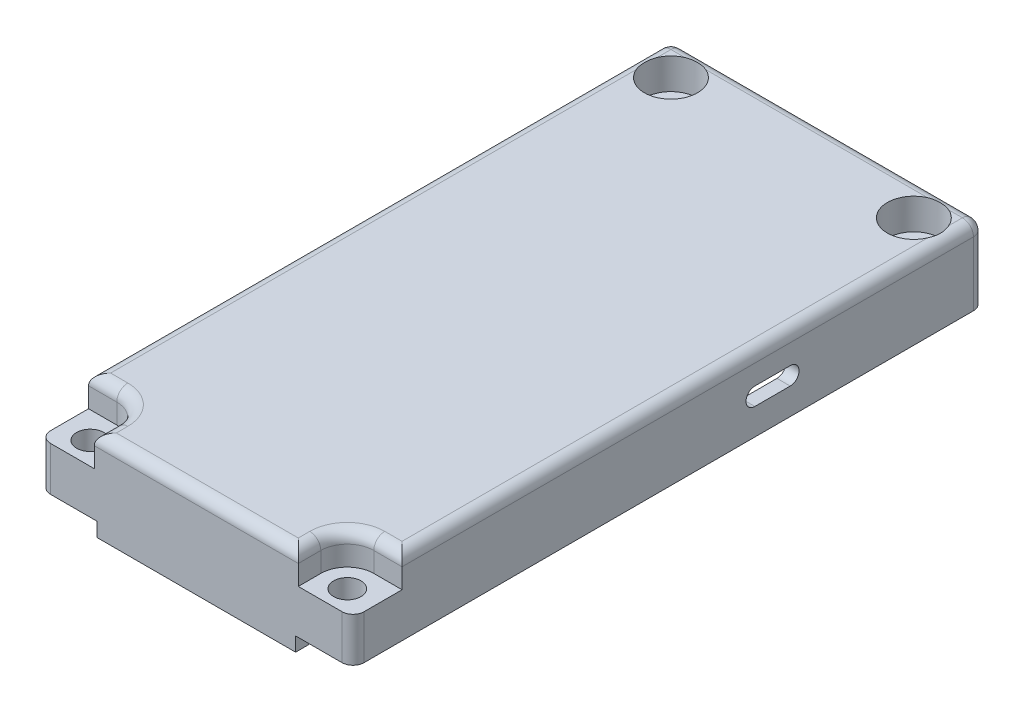
SolidWorks part; units mm, degrees
ref_plane "Front Plane" through (0, 0, 0) normal (0, 0, 1) x (1, 0, 0)
ref_plane "Top Plane" through (0, 0, 0) normal (0, 1, 0) x (1, 0, 0)
ref_plane "Right Plane" through (0, 0, 0) normal (1, 0, 0) x (0, 0, -1)
sketch "Sketch1" plane through (0, 0, 0) normal (0, 1, 0) x (1, 0, 0)
  line L1 (0, 0) -> (35.5, 0)
  line L2 (0, 0) -> (0, 71.5)
  line L3 (0, 71.5) -> (35.5, 71.5)
  line L4 (35.5, 0) -> (35.5, 71.5)
  dimension "D1" = 71.5
  dimension "D2" = 35.5
extrude "Boss-Extrude1" add sketch "Sketch1" along normal blind 8.5
sketch "Sketch2" plane through (0, 0, 0) normal (0, -1, 0) x (1, 0, 0)
  line L0 (0, -71.5) -> (0, 0) construction
  line L1 (1.5, -1.5) -> (34, -1.5)
  line L2 (1.5, -1.5) -> (1.5, -64.25)
  line L3 (1.5, -64.25) -> (34, -64.25)
  line L4 (34, -1.5) -> (34, -64.25)
  line L5 (0, 0) -> (35.5, 0) construction
  line L6 (35.5, 0) -> (35.5, -71.5) construction
  line L7 (35.5, -71.5) -> (0, -71.5) construction
  dimension "D1" = 1.5
  dimension "D2" = 1.5
  dimension "D3" = 1.5
  dimension "D4" = 7.25
extrude "Cut-Extrude1" cut sketch "Sketch2" against normal offset from surface (7 mm away) 1.5 up to face at (17.75, 8.5, -35.75)
sketch "Sketch3" plane through (0, 0, 0) normal (0, -1, 0) x (-1, 0, 0)
  line L0 (0, 0) -> (-35.5, 0) construction
  line L1 (-6.5, 0) -> (-29, 0)
  line L2 (-6.5, 0) -> (-6.5, 1.5)
  line L3 (-6.5, 1.5) -> (-29, 1.5)
  line L4 (-29, 0) -> (-29, 1.5)
  line L5 (-1.5, 1.5) -> (-34, 1.5) construction
  line L15 (-34, 64.25) -> (-34, 1.5) construction
  line L16 (-1.5, 1.5) -> (-1.5, 64.25) construction
  dimension "D1" = 5
  dimension "D2" = 5
extrude "Boss-Extrude2" add sketch "Sketch3" along normal blind 1.6
sketch "Sketch4" plane through (0, 0, -71.5) normal (0, 0, -1) x (-1, 0, 0)
  line L0 (-35.5, 0) -> (0, 0) construction
  line L1 (-25.5, 0) -> (-10, 0)
  line L2 (-25.5, 0) -> (-25.5, 1.25)
  line L3 (-25.5, 1.25) -> (-10, 1.25)
  line L4 (-10, 0) -> (-10, 1.25)
  line L7 (-35.5, 8.5) -> (-35.5, 0) construction
  line L8 (0, 8.5) -> (0, 0) construction
  dimension "D1" = 10
  dimension "D2" = 10
  dimension "D3" = 1.25
extrude "Cut-Extrude2" cut sketch "Sketch4" against normal blind 6.5
fillet "Fillet1" radius 1.25 2 edges at (25.5, 1.25, -68.25) (10, 1.25, -68.25)
sketch "Sketch5" plane through (0, 0, 0) normal (0, -1, 0) x (1, 0, 0)
  line L1 (13.25, -65) -> (22.25, -65)
  line L2 (13.25, -65) -> (13.25, -64.25)
  line L3 (13.25, -64.25) -> (22.25, -64.25)
  line L4 (22.25, -65) -> (22.25, -64.25)
  line L6 (34, -64.25) -> (1.5, -64.25) construction
  line L7 (25.5, -65) -> (10, -65) construction
  line L8 (34, -1.5) -> (34, -64.25) construction
  point P5 (0, 0)
  point P7 (0, 0)
  point P12 (17.75, -64.25)
  dimension "D1" = 9
  dimension "D2" = 16.25
extrude "Boss-Extrude3" add sketch "Sketch5" along normal blind 1.6
sketch "Sketch7" plane through (0, 7, 0) normal (0, -1, 0) x (1, 0, 0)
  line L0 (34, -1.5) -> (29, -1.5) construction
  line L1 (28, -1.5) -> (34, -1.5)
  line L2 (28, -1.5) -> (28, -7.5)
  line L3 (28, -7.5) -> (34, -7.5)
  line L4 (34, -1.5) -> (34, -7.5)
  line L5 (34, -1.5) -> (34, -64.25) construction
  line L6 (1.5, -1.5) -> (34, -1.5) construction
  line L7 (7.5, -1.5) -> (1.5, -1.5)
  line L8 (7.5, -1.5) -> (7.5, -7.5)
  line L9 (7.5, -7.5) -> (1.5, -7.5)
  line L10 (1.5, -1.5) -> (1.5, -7.5)
  line L11 (1.5, -64.25) -> (1.5, -1.5) construction
  dimension "D1" = 6
extrude "Boss-Extrude4" add sketch "Sketch7" along normal up to surface (7 mm away) up to face at (29.25, 0, -40.45)
sketch "Sketch8" plane through (0, 0, 0) normal (0, -1, 0) x (-1, 0, 0)
  line L0 (-35.5, 71.5) -> (-25.5, 71.5) construction
  line L1 (-35.5, 0) -> (-35.5, 71.5) construction
  line L2 (0, 71.5) -> (0, 0) construction
  circle A0 centre (-32.3, 2.55) radius 1.55
  circle A1 centre (-31.5, 67.5) radius 1.55
  circle A2 centre (-4, 67.5) radius 1.55
  circle A3 centre (-3.2, 2.55) radius 1.55
  point P8 (-4.5383, 3.3439)
  point P9 (-32.1566, 67.038)
  point P10 (0, 0)
  point P11 (0, 0)
  dimension "D7" = 3.1
  dimension "D1" = 4
  dimension "D2" = 4
  dimension "D3" = 4
  dimension "D4" = 3.2
  dimension "D5" = 3.2
  dimension "D6" = 2.55
extrude "Cut-Extrude3" cut sketch "Sketch8" against normal through all
sketch "Sketch9" plane through (0, 8.5, 0) normal (0, 1, 0) x (1, 0, 0)
  line L0 (3.2, 5.55) -> (0, 5.55)
  line L1 (0, 71.5) -> (0, 0) construction
  line L2 (0, 5.55) -> (0, 0)
  line L3 (0, 0) -> (6.2, 0)
  line L4 (0, 0) -> (35.5, 0) construction
  line L5 (6.2, 0) -> (6.2, 2.55)
  line L10 (29.3, 2.55) -> (29.3, 0)
  line L11 (29.3, 0) -> (35.5, 0)
  line L12 (35.5, 0) -> (35.5, 5.55)
  line L13 (35.5, 0) -> (35.5, 71.5) construction
  line L14 (35.5, 5.55) -> (32.3, 5.55)
  circle A0 centre (4, 67.5) radius 3
  circle A1 centre (31.5, 67.5) radius 3
  arc A3 (6.2, 2.55) -> (3.2, 5.55) centre (3.2, 2.55) ccw
  arc A4 (32.3, 5.55) -> (29.3, 2.55) centre (32.3, 2.55) ccw
  dimension "D1" = 6
  dimension "D2" = 3
  dimension "D3" = 3
extrude "Cut-Extrude4" cut sketch "Sketch9" against normal offset from surface (3.5 mm away) 5 up to face at (3.2, 0, -4.1)
sketch "Sketch10" plane through (34, 0, 0) normal (-1, 0, 0) x (0, 0, 1)
  line L0 (-49.5, 4) -> (-45.5, 4) construction
  line L1 (-49.5, 5) -> (-45.5, 5)
  line L2 (-49.5, 3) -> (-45.5, 3)
  line L3 (-7.5, 7) -> (-64.25, 7) construction
  line L4 (-7.5, 0) -> (-7.5, 7) construction
  arc A0 (-49.5, 5) -> (-49.5, 3) centre (-49.5, 4) ccw
  arc A1 (-45.5, 3) -> (-45.5, 5) centre (-45.5, 4) ccw
  point P2 (-47.5, 4)
  dimension "D1" = 2
  dimension "D2" = 4
  dimension "D3" = 3
  dimension "D4" = 40
extrude "Cut-Extrude5" cut sketch "Sketch10" against normal through all
sketch "Sketch11" plane through (0, 7, 0) normal (0, -1, 0) x (1, 0, 0)
  line L1 (34, -64.25) -> (1.5, -64.25) construction
  line L2 (1.5, -64.25) -> (6.5, -64.25)
  line L3 (1.5, -64.25) -> (1.5, -59.25)
  line L4 (1.5, -59.25) -> (6.5, -59.25)
  line L6 (6.5, -64.25) -> (6.5, -59.25)
  line L7 (1.5, -64.25) -> (1.5, -7.5) construction
  line L9 (34, -64.25) -> (29, -64.25)
  line L10 (34, -64.25) -> (34, -59.25)
  line L11 (34, -59.25) -> (29, -59.25)
  line L12 (29, -64.25) -> (29, -59.25)
  dimension "D1" = 5
extrude "Boss-Extrude8" add sketch "Sketch11" along normal offset from surface (4.31 mm away) 2.69 up to face at (3.2, 0, -4.1)
fillet "Fillet2" radius 1.25 14 edges at (17.75, 8.5, -71.5) (35.5, 8.5, -38.525) (33.9, 8.5, -5.55) (30.1787, 8.5, -4.6713) (29.3, 8.5, -1.275) (17.75, 8.5, 0) (6.2, 8.5, -1.275) (5.3213, 8.5, -4.6713) (1.6, 8.5, -5.55) (0, 8.5, -38.525) (0, 2.5, 0) (35.5, 2.5, 0) (35.5, 4.25, -71.5) (0, 4.25, -71.5)
